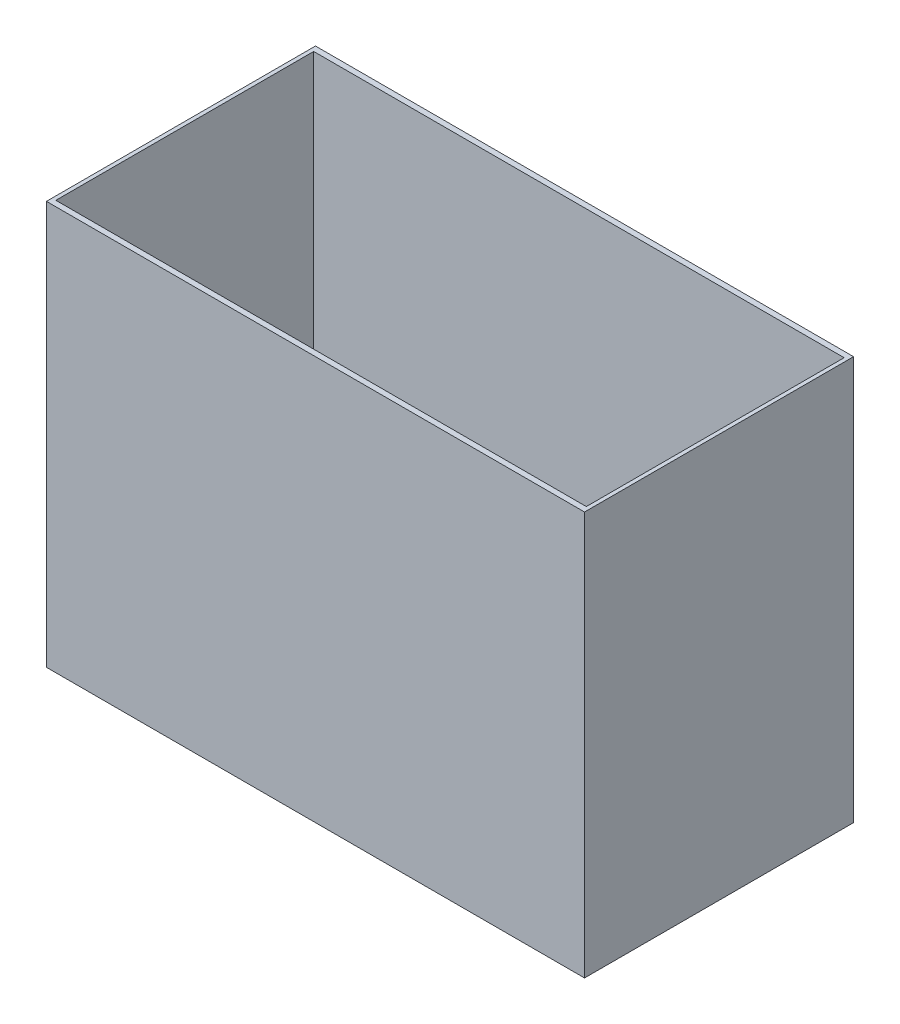
SolidWorks part; units mm, degrees
ref_plane "Front Plane" through (0, 0, 0) normal (0, 0, 1) x (1, 0, 0)
ref_plane "Top Plane" through (0, 0, 0) normal (0, 1, 0) x (1, 0, 0)
ref_plane "Right Plane" through (0, 0, 0) normal (1, 0, 0) x (0, 0, -1)
other "Bounding Box"
ref_plane "Default Plane" through (-292.1, 0, -139.7) normal (0, 1, 0) x (1, 0, 0)
sketch "Sketch1" plane through (0, 0, 0) normal (0, 1, 0) x (1, 0, 0)
  line L0 (-292.1, 0) -> (292.1, 0) construction
  line L1 (-292.1, 139.7) -> (292.1, 139.7)
  line L2 (-292.1, 139.7) -> (-292.1, -139.7)
  line L3 (-292.1, -139.7) -> (292.1, -139.7)
  line L4 (292.1, 139.7) -> (292.1, -139.7)
  line L5 (0, 139.7) -> (0, -139.7) construction
  point P8 (0, 0)
  dimension "D1" = 584.2
  dimension "D2" = 279.4
extrude "Boss-Extrude1" add sketch "Sketch1" along normal blind 6.35
sketch "Sketch2" plane through (0, 6.35, 0) normal (0, 1, 0) x (1, 0, 0)
  line L0 (-245.9259, -63.5) -> (-55.3589, -63.5) construction
  line L1 (-241.3, -120.6497) -> (-152.4, -120.6497)
  line L2 (-241.3, -120.6497) -> (-241.3, -101.5997)
  line L3 (-241.3, -101.5997) -> (-152.4, -101.5997)
  line L4 (-152.4, -120.6497) -> (-152.4, -101.5997)
  line L5 (-241.3, -120.6497) -> (-152.4, -101.5997) construction
  line L6 (-241.3, -101.5997) -> (-152.4, -120.6497) construction
  line L7 (-292.1, 139.7) -> (-292.1, -139.7) construction
  line L8 (-292.1, 0) -> (292.1, 0) construction
  line L9 (292.1, -139.7) -> (292.1, 139.7) construction
  line L10 (0, 0) -> (0, 121.6784) construction
  line L11 (241.3, -101.5997) -> (152.4, -120.6497) construction
  line L12 (241.3, -120.6497) -> (152.4, -101.5997) construction
  line L13 (152.4, -120.6497) -> (152.4, -101.5997)
  line L14 (241.3, -101.5997) -> (152.4, -101.5997)
  line L15 (241.3, -120.6497) -> (241.3, -101.5997)
  line L16 (241.3, -120.6497) -> (152.4, -120.6497)
  point P0 (-196.85, -111.1247)
  point P17 (196.85, -111.1247)
  dimension "D1" = 19.05
  dimension "D2" = 88.9
  dimension "D3" = 38.0997
  dimension "D4" = 50.8
  dimension "D5" = 63.5
extrude "Boss-Extrude2" [suppressed] add sketch "Sketch2" along normal blind 304.8 separate body contours L2 L1 L4 L3
pattern_linear "LPattern1" [suppressed] count 2 spacing 304.8 of bodies 101
pattern_linear "LPattern2" [suppressed] count 2 spacing 215.9 of bodies 101
sketch "Sketch3" plane through (0, 0, 0) normal (0, 1, 0) x (1, 0, 0)
  line L1 (-304.8, -152.4) -> (304.8, -152.4)
  line L2 (-304.8, -152.4) -> (-304.8, 152.4)
  line L3 (-304.8, 152.4) -> (304.8, 152.4)
  line L4 (304.8, -152.4) -> (304.8, 152.4)
  line L5 (-304.8, -152.4) -> (304.8, 152.4) construction
  line L6 (-304.8, 152.4) -> (304.8, -152.4) construction
  line L7 (-300.482, -146.05) -> (300.482, -146.05)
  line L8 (-300.482, -146.05) -> (-300.482, 146.05)
  line L9 (-300.482, 146.05) -> (300.482, 146.05)
  line L10 (300.482, -146.05) -> (300.482, 146.05)
  line L11 (-300.482, -146.05) -> (300.482, 146.05) construction
  line L12 (-300.482, 146.05) -> (300.482, -146.05) construction
  point P0 (0, 0)
  point P6 (0, 0)
  dimension "D1" = 609.6
  dimension "D2" = 304.8
  dimension "D3" = 292.1
  dimension "D4" = 600.964
extrude "Boss-Extrude3" add sketch "Sketch3" along normal blind 457.2 separate body
sketch "Sketch4" plane through (0, 6.35, 0) normal (0, 1, 0) x (1, 0, 0)
  circle A0 centre (273.05, 120.65) radius 2.7781
  circle A1 centre (273.05, 120.65) radius 2.7781 construction
  dimension "D1" = 5.5562
extrude "Cut-Extrude1" cut sketch "Sketch4" against normal through all
mirror "Mirror1" about plane through (0, 0, 0) normal (0, 0, 1) of "Cut-Extrude1"
